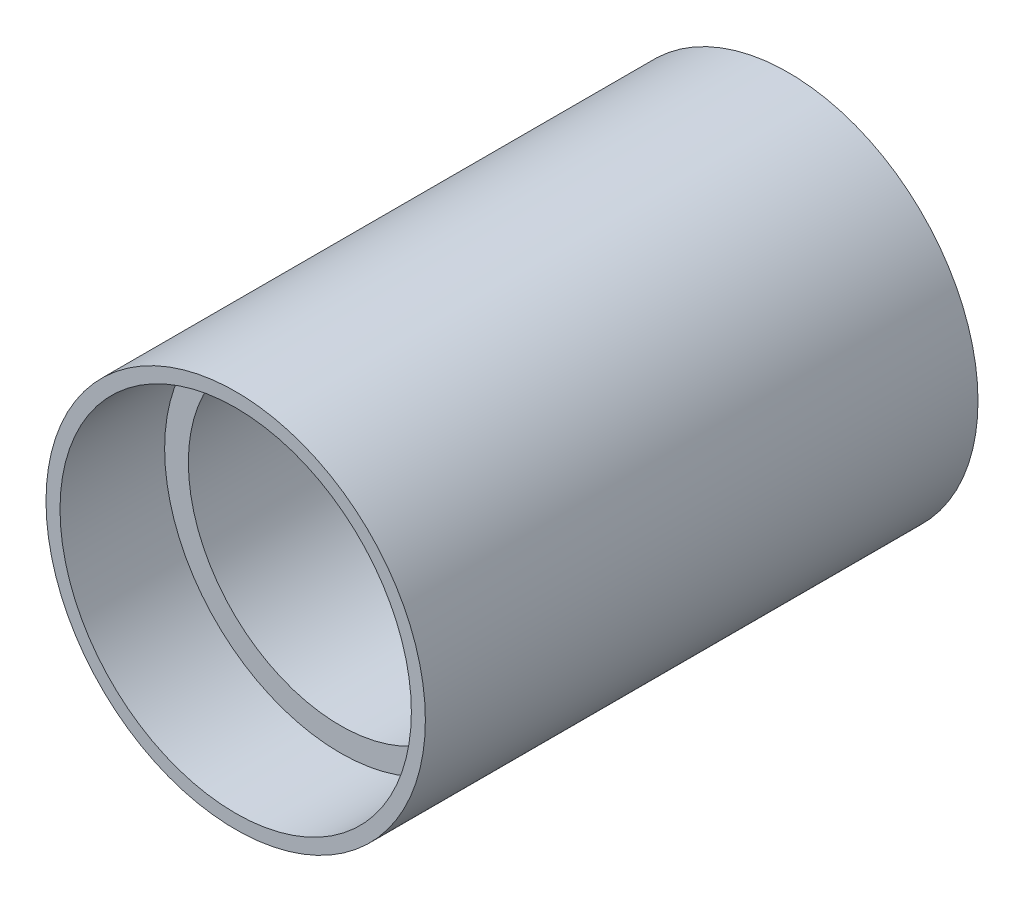
SolidWorks part; units mm, degrees
ref_plane "Top Plane" through (0, 0, 0) normal (0, 0, 1) x (1, 0, 0)
ref_plane "Front Plane" through (0, 0, 0) normal (0, 1, 0) x (1, 0, 0)
ref_plane "Right Plane" through (0, 0, 0) normal (1, 0, 0) x (0, 0, -1)
sketch "Profile Sketch" plane through (0, 0, 0) normal (0, 0, 1) x (1, 0, 0)
  circle A0 centre (0, 0) radius 12.7
  dimension "D1" = 25.4
extrude "Profile Extrude" add sketch "Profile Sketch" along normal blind 37
sketch "Bore Sketch" plane through (0, 0, 0) normal (0, 0, -1) x (-1, 0, 0)
  circle A0 centre (0, 0) radius 10.1745
  dimension "D1" = 20.349
extrude "Bore Cut" cut sketch "Bore Sketch" against normal through all
sketch "Bearing Pocket 1 Sketch" plane through (0, 0, 0) normal (0, 0, -1) x (-1, 0, 0)
  circle A1 centre (0, 0) radius 11.762
  dimension "D1" = 23.524
extrude "Bearing Pocket 1 Cut" cut sketch "Bearing Pocket 1 Sketch" against normal blind 7.005
sketch "Bearing Pocket 2 Sketch" plane through (0, 0, 37) normal (0, 0, 1) x (1, 0, 0)
  circle A0 centre (0, 0) radius 11.762
  dimension "D1" = 23.524
extrude "Bearing Pocket 2 Cut" cut sketch "Bearing Pocket 2 Sketch" against normal blind 7.005
ref_plane "Cylinder Tanget Plane" through (-12.7, 0, 0) normal (-1, 0, 0) x (0, 0, 1)
sketch "Cylinder Tangent Centering Sketch" plane through (-12.7, 0, 0) normal (-1, 0, 0) x (0, 0, 1)
  line L0 (0, 12.7) -> (0, -12.7) construction
  line L1 (37, -12.7) -> (37, 12.7) construction
  line L2 (0, 12.7) -> (0, -12.7) construction
  line L3 (37, -12.7) -> (37, 12.7) construction
  line L4 (37, 0) -> (0, 0) construction
  point P6 (18.5, 0)
ref_plane "Cylinder Cross Section Plane" through (0, 0, 18.5) normal (0, 0, -1) x (-1, 0, 0)
sketch "Cylinder Cross Section Sketch" plane through (0, 0, 18.5) normal (0, 0, -1) x (-1, 0, 0)
  circle A0 centre (0, 0) radius 12.7 construction
  circle A1 centre (0, 0) radius 12.7 construction
equation "\"bearing_pocket_diameter\"=0.926142"
equation "\"D1@Bearing Pocket 1 Sketch\"=\"bearing_pocket_diameter\""
equation "\"bearing_pocket_depth\"=0.275787"
equation "\"D1@Bearing Pocket 1 Cut\"=\"bearing_pocket_depth\""
equation "\"D1@Bearing Pocket 2 Sketch\"=\"bearing_pocket_diameter\""
equation "\"D1@Bearing Pocket 2 Cut\"=\"bearing_pocket_depth\""
equation "\"D1@Bore Sketch\"=\"bearing_pocket_diameter\"-0.125"
